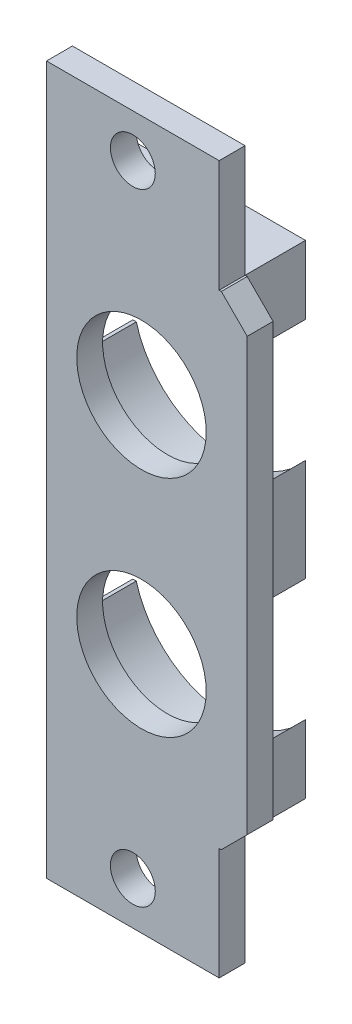
SolidWorks part; units mm, degrees
material "PET"
ref_plane "Front Plane" through (0, 0, 0) normal (0, 0, 1) x (1, 0, 0)
ref_plane "Top Plane" through (0, 0, 0) normal (0, 1, 0) x (1, 0, 0)
ref_plane "Right Plane" through (0, 0, 0) normal (1, 0, 0) x (0, 0, -1)
sketch "Sketch9" plane through (0, 0, 0) normal (0, 0, 1) x (1, 0, 0)
  line L0 (10, 31) -> (-10, -31) construction
  line L1 (10, 31) -> (-10, 31)
  line L2 (10, 31) -> (10, 20.0711)
  line L3 (10, -31) -> (-10, -31)
  line L4 (-10, 31) -> (-10, 15.9732)
  line L5 (10, -31) -> (-10, -41) construction
  line L6 (10, -31) -> (-10, -31)
  line L7 (10, -31) -> (10, -41)
  line L8 (10, -41) -> (-10, -41)
  line L9 (-10, -31) -> (-10, -41)
  line L10 (-10, 31) -> (10, 31)
  line L11 (-10, 31) -> (-10, 41)
  line L12 (-10, 41) -> (10, 41)
  line L13 (10, 31) -> (10, 41)
  line L14 (10, 41) -> (-10, 31) construction
  line L16 (10, 5.9289) -> (10, -5.9289)
  line L17 (10, -20.0711) -> (10, -31)
  line L18 (-9.6, 15.9732) -> (-10, 15.9732)
  line L19 (-9.6, 10.0268) -> (-10, 10.0268)
  line L20 (-10, 10.0268) -> (-10, -10.0268)
  line L21 (-9.6, -10.0268) -> (-10, -10.0268)
  line L22 (-9.6, -15.9732) -> (-10, -15.9732)
  line L23 (-10, -15.9732) -> (-10, -31)
  line L24 (-10, 31) -> (10, 31)
  line L25 (-10, 31) -> (-10, 28)
  line L26 (-10, 28) -> (10, 28)
  line L27 (10, 31) -> (10, 28)
  line L28 (-10, -31) -> (10, -31)
  line L29 (-10, -31) -> (-10, -28)
  line L30 (-10, -28) -> (10, -28)
  line L31 (10, -31) -> (10, -28)
  circle A0 centre (0, -36) radius 2.6
  circle A1 centre (0, 36) radius 2.6
  arc A2 (10, 20.0711) -> (-9.6, 15.9732) centre (1.25, 13) ccw
  arc A3 (10, -5.9289) -> (-9.6, -10.0268) centre (1.25, -13) ccw
  arc A4 (-9.6, 10.0268) -> (10, 5.9289) centre (1.25, 13) ccw
  arc A5 (-9.6, -15.9732) -> (10, -20.0711) centre (1.25, -13) ccw
  point P4 (0, 0)
  point P15 (0, -36)
  point P17 (0, 36)
  dimension "D2" = 5.2
  dimension "D3" = 5.2
  dimension "D6" = 22.5
  dimension "D7" = 22.5
  dimension "D9" = 18
  dimension "D1" = 20
  dimension "D4" = 10
  dimension "D5" = 10
  dimension "D8" = 18
  dimension "D10" = 26
  dimension "D11" = 0.4
  dimension "D12" = 0.4
  dimension "D13" = 0.4
  dimension "D14" = 0.4
  dimension "D15" = 3
  dimension "D16" = 3
sketch "Sketch10" plane through (0, 0, 0) normal (0, 0, 1) x (1, 0, 0)
  line L0 (10, 31) -> (-10, -31) construction
  line L1 (10, 31) -> (-10, 31)
  line L2 (10, 31) -> (10, 19.3246)
  line L3 (10, -31) -> (-10, -31)
  line L4 (-10, 31) -> (-10, 15.1012)
  line L5 (10, -31) -> (-10, -41) construction
  line L6 (10, -31) -> (-10, -31)
  line L7 (10, -31) -> (10, -41)
  line L8 (10, -41) -> (-10, -41)
  line L9 (-10, -31) -> (-10, -41)
  line L10 (-10, 31) -> (10, 31)
  line L11 (-10, 31) -> (-10, 41)
  line L12 (-10, 41) -> (10, 41)
  line L13 (10, 31) -> (10, 41)
  line L14 (10, 41) -> (-10, 31) construction
  line L16 (10, 19.3246) -> (10, -17.4092)
  line L17 (10, -17.4092) -> (10, -31)
  line L20 (-10, 15.1012) -> (-10, -10.0606)
  line L23 (-10, -10.0606) -> (-10, -31)
  circle A0 centre (0, -36) radius 2.6
  circle A1 centre (0, 36) radius 2.6
  arc A2 (10, 19.3246) -> (7.1381, 22.1282) centre (1, 13) ccw
  circle A6 centre (1, 13) radius 7.5
  circle A7 centre (1, -13) radius 7.5
  point P4 (0, 0)
  point P15 (0, -36)
  point P17 (0, 36)
  dimension "D2" = 5.2
  dimension "D3" = 5.2
  dimension "D6" = 22
  dimension "D7" = 18
  dimension "D15" = 15
  dimension "D16" = 15
  dimension "D1" = 20
  dimension "D4" = 10
  dimension "D5" = 10
  dimension "D8" = 18
  dimension "D10" = 26
extrude "Boss-Extrude7" add sketch "Sketch10" against normal blind 3 contours L1 L13 L12 L11 A1 | L20 L23 L3 L17 L16 L2 L1 L4 A7 A6 | L3 L9 L8 L7 A0 region at (-0.3986, 0, 0) region at (0, 31.2236, 0) region at (9.7764, -36, 0)
extrude "Boss-Extrude10" add sketch "Sketch9" against normal offset from surface (10 mm away) 7 contours A4 L19 L20 L21 A3 L16 | A2 L2 L26 L4 L18 | A5 L22 L23 L30 L17 region at (-0.9893, 24.8045, 0) region at (-0.9893, -24.8045, 0) region at (-1.5323, 0, 0) up to face at (2.6, 36, -3) offset beyond the face yes
sketch "Sketch12" plane through (0, 0, -3) normal (0, 0, -1) x (-1, 0, 0)
  line L0 (10, -28) -> (-10, -28) construction
  line L1 (-10, 28) -> (-13.25, 28)
  line L2 (-10, 28) -> (-10, -28)
  line L3 (-10, -28) -> (-13.25, -28)
  line L4 (-13.25, 28) -> (-13.25, -28)
  arc A0 (9.6, 15.9732) -> (-10, 20.0711) centre (-1.25, 13) ccw construction
  dimension "D1" = 12
extrude "Boss-Extrude11" add sketch "Sketch12" against normal blind 3
chamfer "Chamfer2" distance 3 angle 45 1 edges at (13.25, -28, -1.5)
chamfer "Chamfer3" distance 3 angle 45 1 edges at (13.25, 28, -1.5)
